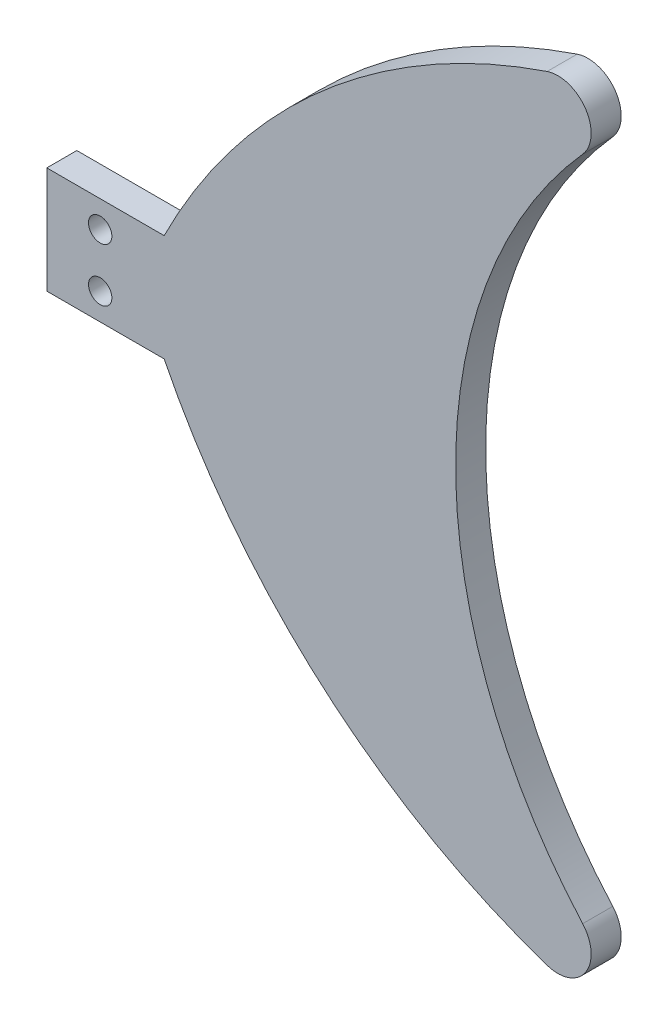
SolidWorks part; units mm, degrees
ref_plane "前视基准面" through (0, 0, 0) normal (0, 0, 1) x (1, 0, 0)
ref_plane "上视基准面" through (0, 0, 0) normal (0, 1, 0) x (1, 0, 0)
ref_plane "右视基准面" through (0, 0, 0) normal (1, 0, 0) x (0, 0, -1)
sketch "草图1" plane through (0, 0, 0) normal (0, 0, 1) x (1, 0, 0)
  line L0 (-43.1897, 0) -> (51.145, 0) construction
  line L1 (0, 42.1426) -> (0, -43.1152) construction
  line L2 (6, 12) -> (37.7485, 60)
  line L3 (-6, -12) -> (6, -12)
  line L4 (-6, -12) -> (-6, 12)
  line L5 (-6, 12) -> (6, 12)
  line L7 (-6, -12) -> (6, 12) construction
  line L8 (-6, 12) -> (6, -12) construction
  line L9 (6, -12) -> (37.7485, -60)
  arc A0 (37.7485, -60) -> (37.7485, 60) centre (-1.9371, 0) ccw
  point P5 (0, 0)
  dimension "D4" = 70
  dimension "D1" = 24
  dimension "D2" = 12
  dimension "D3" = 120
extrude "凸台-拉伸1" add sketch "草图1" along normal blind 4.5
sketch "草图2" plane through (0, 0, 4.5) normal (0, 0, 1) x (1, 0, 0)
  line L0 (-6, 0) -> (7.5637, 0) construction
  line L1 (-6, 12) -> (-6, -12) construction
  circle A0 centre (0, 5) radius 1.25
  circle A1 centre (0, -5) radius 1.25
  dimension "D1" = 10
  dimension "D2" = 2.5
  dimension "D3" = 6
extrude "切除-拉伸1" cut sketch "草图2" against normal blind 10
sketch "草图3" plane through (0, 0, 4.5) normal (0, 0, 1) x (1, 0, 0)
  line L0 (37.7485, 60) -> (6, 12) construction
  line L1 (-6, 12) -> (6, 12)
  line L2 (-6, 12) -> (-6, 10)
  line L3 (-6, 10) -> (6, 10)
  line L4 (6, 12) -> (6, 10)
  line L6 (-6, -12) -> (6, -12)
  line L7 (-6, -12) -> (-6, -10)
  line L8 (-6, -10) -> (6, -10)
  line L9 (6, -12) -> (6, -10)
  dimension "D1" = 2
  dimension "D2" = 2
extrude "切除-拉伸2" cut sketch "草图3" against normal blind 10
sketch "草图4" plane through (0, 0, 4.5) normal (0, 0, 1) x (1, 0, 0)
  line L1 (9, -15) -> (-4, -15)
  line L2 (9, -15) -> (9, 15)
  line L3 (9, 15) -> (-4, 15)
  line L4 (-4, -15) -> (-4, 15)
  line L6 (-6, 0) -> (9, 0) construction
  line L7 (-6, 10) -> (-6, -10) construction
  line L8 (6, 10) -> (6, 12) construction
  dimension "D1" = 10
  dimension "D2" = 30
  dimension "D3" = 13
extrude "凸台-拉伸2" add sketch "草图4" along normal blind 4
sketch "草图5" plane through (0, 0, 0) normal (0, 0, -1) x (-1, 0, 0)
  line L0 (-7.9843, 15) -> (4, 15) construction
  line L1 (4, -15) -> (-9, -15)
  line L2 (4, -15) -> (4, 15)
  line L3 (4, 15) -> (-9, 15)
  line L4 (-9, -15) -> (-9, 15)
  dimension "D1" = 13
extrude "凸台-拉伸3" add sketch "草图5" along normal blind 4
sketch "草图6" plane through (0, 15, 0) normal (0, 1, 0) x (1, 0, 0)
  line L1 (9, 4) -> (-4, 4)
  line L2 (9, 4) -> (9, -8.5)
  line L3 (9, -8.5) -> (-4, -8.5)
  line L4 (-4, 4) -> (-4, -8.5)
extrude "凸台-拉伸4" add sketch "草图6" against normal blind 3
mirror "镜向1" about plane through (0, 0, 0) normal (0, 1, 0) of "凸台-拉伸4"
ref_plane "基准面1" through (0, 0, 2.25) normal (0, 0, 1) x (1, 0, 0)
sketch "草图8" plane through (0, 0, 2.25) normal (0, 0, 1) x (1, 0, 0)
  line L0 (-4, 15) -> (37.7485, 60)
  line L2 (-4, 15) -> (7.9843, 15)
  line L3 (7.9843, 15) -> (37.7485, 60)
extrude "凸台-拉伸5" add sketch "草图8" along normal up to surface and the other way up to surface up to face at (23.6195, 0, 4.5) other way up to face at (23.6195, 0, 0)
mirror "镜向2" about plane through (0, 0, 0) normal (0, 1, 0) of "凸台-拉伸5"
sketch "草图9" plane through (-4, 0, 0) normal (-1, 0, 0) x (0, 0, 1)
  line L0 (0, 10) -> (0, 12)
  line L1 (0, 12) -> (4.5, 12)
  line L2 (4.5, 12) -> (4.5, 10)
  line L3 (4.5, -10) -> (4.5, -12)
  line L4 (0, 10) -> (0, -10)
  line L5 (0, -10) -> (4.5, -10)
  line L6 (4.5, -10) -> (4.5, 10)
  line L7 (4.5, 10) -> (0, 10)
  line L8 (0, 10) -> (0, -10)
  line L9 (4.5, -12) -> (0, -12)
  line L10 (4.5, -10) -> (4.5, 10)
  line L11 (0, -12) -> (0, -10)
  dimension "D1" = 0
extrude "切除-拉伸3" cut sketch "草图9" against normal blind 10.5 and the other way blind 3
sketch "草图14" plane through (0, 0, 8.5) normal (0, 0, 1) x (1, 0, 0)
  line L4 (-4, 15) -> (-4, -15)
  line L5 (-4, -15) -> (9, -15)
  line L6 (9, -15) -> (9, 15)
  line L7 (9, 15) -> (-4, 15)
  line L8 (-4, 15) -> (-4, -15)
  line L9 (-4, -15) -> (9, -15)
  line L10 (9, -15) -> (9, 15)
  line L11 (9, 15) -> (-4, 15)
  dimension "D1" = 0
extrude "切除-拉伸6" cut sketch "草图14" against normal blind 30
sketch "草图16" plane through (0, 0, 4.5) normal (0, 0, 1) x (1, 0, 0)
  line L0 (9, -15) -> (9, 15) construction
  line L1 (9, 15) -> (-4, 15) construction
  line L2 (-4, -15) -> (9, -15) construction
  line L3 (9, -15) -> (9, 15)
  line L4 (9, 15) -> (-4, 15)
  line L5 (-4, -15) -> (9, -15)
  line L6 (-4, 15) -> (-4, -15)
extrude "凸台-拉伸6" add sketch "草图16" against normal up to surface (4.5 mm away) up to face at (19.6248, 0, 0)
sketch "草图17" plane through (0, 0, 4.5) normal (0, 0, 1) x (1, 0, 0)
  arc A0 (37.7485, -60) -> (37.7485, 60) centre (-1.9371, 0) ccw construction
  point P0 (70, 0)
sketch "草图18" plane through (0, 0, 4.5) normal (0, 0, 1) x (1, 0, 0)
  line L0 (-4, 0) -> (70, 0) construction
  line L1 (-4, 15) -> (-4, -15) construction
  line L2 (-4, 15) -> (65.3824, 15) construction
  line L3 (-4, -15) -> (65.3824, -15) construction
  line L4 (37.7485, 60) -> (6, 15)
  line L5 (6, 15) -> (-4, 15)
  line L6 (-4, 15) -> (37.7485, 60)
  line L7 (-4, -15) -> (37.7485, -60)
  line L8 (6, -15) -> (-4, -15)
  line L9 (37.7485, -60) -> (6, -15)
  dimension "D1" = 10
extrude "切除-拉伸7" cut sketch "草图18" against normal blind 30
sketch "草图19" plane through (-4, 0, 0) normal (-1, 0, 0) x (0, 0, 1)
  line L0 (2.25, -15) -> (2.25, 15) construction
  line L1 (2.25, -39.9189) -> (2.25, 39.9189) construction
  line L2 (4.5, 15) -> (0, 15) construction
  line L3 (4.5, 0) -> (0, 0) construction
  ellipse E0 centre (2.25, 0) end of major axis (2.25, 16) minor radius 9
  dimension "D1" = 32
  dimension "D2" = 18
extrude "凸台-拉伸7" add sketch "草图19" along normal blind 1 and the other way blind 12
sketch "草图20" plane through (-5, 0, 0) normal (-1, 0, 0) x (0, 0, 1)
  line L0 (-6.75, 0) -> (11.25, 0) construction
  line L1 (2.25, 16) -> (2.25, -16) construction
  line L2 (2.25, -39.9189) -> (2.25, 39.9189) construction
  line L4 (0, -8.25) -> (4.5, -8.25)
  line L5 (0, -8.25) -> (0, 8.25)
  line L6 (0, 8.25) -> (4.5, 8.25)
  line L7 (4.5, -8.25) -> (4.5, 8.25)
  ellipse E0 centre (2.25, 0) end of major axis (2.25, 16) minor radius 9 construction
  dimension "D1" = 16.5
  dimension "D2" = 4.5
extrude "切除-拉伸8" cut sketch "草图20" against normal blind 10.5
ref_plane "基准面2" through (5, 0, 0) normal (-1, 0, 0) x (0, 0, 1)
sketch "草图21" plane through (5, 0, 0) normal (-1, 0, 0) x (0, 0, 1)
  ellipse E0 centre (2.25, 0) end of major axis (2.25, 19) minor radius 12
  ellipse E1 centre (2.25, 0) end of major axis (2.25, 16) minor radius 9
  ellipse E2 centre (2.25, 0) end of major axis (2.25, 16) minor radius 9
  dimension "D2" = 38
  dimension "D3" = 24
  dimension "D1" = 0
extrude "凸台-拉伸8" add sketch "草图21" against normal blind 5
sketch "草图23" plane through (0, 0, 4.5) normal (0, 0, 1) x (1, 0, 0)
  line L0 (5, 19) -> (37.7485, 60)
  line L1 (5, 19) -> (5, -19) construction
  line L9 (8.8221, 19) -> (5, 19) construction
  line L16 (5, 19) -> (5, 17.2677)
  line L17 (5, 17.2677) -> (10, 17.2677)
  line L18 (10, -18.663) -> (10, 18.663) construction
  line L19 (10, 17.2677) -> (37.7485, 60)
extrude "凸台-拉伸9" add sketch "草图23" against normal up to surface (4.5 mm away) up to face at (18.0917, 0, 0)
mirror "镜向4" about plane through (0, 0, 0) normal (0, 1, 0) of "凸台-拉伸9"
sketch "草图24" plane through (5, 0, 0) normal (-1, 0, 0) x (0, 0, 1)
  line L0 (2.25, -39.9189) -> (2.25, 39.9189) construction
  ellipse E0 centre (2.25, 0) end of major axis (2.25, 16) minor radius 9 construction
  ellipse E1 centre (2.25, 0) end of major axis (2.25, 16) minor radius 9
  ellipse E2 centre (0, 0) end of major axis (-2.25, 22.2358) minor radius 16.6981
extrude "切除-拉伸9" cut sketch "草图24" against normal blind 1
sketch "草图25" plane through (8, 0, 0) normal (1, 0, 0) x (0, 0, -1)
  line L1 (-4.5, -15.4919) -> (-4.5, 15.4919)
  line L2 (-4.5, -15.4919) -> (-4.5, 15.4919)
  ellipse E1 centre (-2.25, 0) end of major axis (-2.25, 16) minor radius 9 (-4.5, 15.4919) -> (-4.5, -15.4919) ccw
  ellipse E2 centre (-2.25, 0) end of major axis (-2.25, 16) minor radius 9 (-4.5, 15.4919) -> (-4.5, -15.4919) ccw
  dimension "D1" = 0
extrude "凸台-拉伸10" add sketch "草图25" along normal up to surface (2 mm away) up to face at (10, 0, 8.625)
sketch "草图26" plane through (8, 0, 0) normal (1, 0, 0) x (0, 0, -1)
  line L1 (0, 15.4919) -> (0, -15.4919)
  line L2 (0, 15.4919) -> (0, -15.4919)
  ellipse E1 centre (-2.25, 0) end of major axis (-2.25, 16) minor radius 9 (0, -15.4919) -> (0, 15.4919) ccw
  ellipse E2 centre (-2.25, 0) end of major axis (-2.25, 16) minor radius 9 (0, -15.4919) -> (0, 15.4919) ccw
  dimension "D1" = 0
extrude "凸台-拉伸11" add sketch "草图26" along normal up to surface (2 mm away) up to face at (10, 0, -4.125)
sketch "草图27" [suppressed] plane through (0, 0, 4.5) normal (0, 0, 1) x (1, 0, 0)
  line L0 (21.8743, 40.126) -> (121.7706, -39.6657) construction
  line L1 (37.7485, 60) -> (6, 20.252) construction
  line L2 (6, 20.252) -> (37.7485, 60)
  circle A0 centre (77.0023, -3.9073) radius 75
  dimension "D1" = 150
fillet "圆角2" radius 5 2 edges at (37.7485, -60, 2.25) (37.7485, 60, 2.25)
sketch "草图29" plane through (0, 0, 4.5) normal (0, 0, 1) x (1, 0, 0)
  line L0 (-1.9371, 0) -> (96.0443, 0) construction
  line L1 (10, 18.663) -> (10, -18.663) construction
  line L2 (6, 20.252) -> (53.8633, 60)
  line L3 (6, -20.252) -> (53.8633, -60)
  line L4 (6, 20.252) -> (41.159, 69.688)
  line L5 (6, -20.252) -> (41.159, -69.688)
  circle A0 centre (-1.9371, 0) radius 81.9371
  point P3 (80, 0)
  line M1 (6, -20.252) -> (34.7985, -56.3067)
  arc M2 (34.7985, -56.3067) -> (41.7411, -57.1591) centre (38.7053, -53.1862) ccw
  arc M3 (41.7411, -57.1591) -> (41.7411, 57.1591) centre (-1.9371, 0) ccw
  arc M4 (41.7411, 57.1591) -> (34.7985, 56.3067) centre (38.7053, 53.1862) ccw
  line M5 (34.7985, 56.3067) -> (6, 20.252)
  dimension "D1" = 70
  dimension "D2" = 120
extrude "凸台-拉伸12" add sketch "草图29" against normal up to surface (4.5 mm away) contours L0 A0 L2 M3 | L0 L3 A0 M3 region at (66.5477, 30.1694, 4.5) region at (66.5477, -30.1694, 4.5) up to face at (22.499, 0, 0)
extrude "切除-拉伸10" cut sketch "草图29<3>" against normal blind 10 contours L2 A0 L4 M5 M4 M3 | L5 A0 L3 M3 M2 M1 | L3 M1 M2 M3 | L2 M5 M3 M4 region at (29.8636, 44.4089, 4.5) region at (24.1403, 44.5712, 4.5) region at (29.8636, -44.4089, 4.5) region at (49.5406, -57.3046, 4.5)
sketch "草图29<3>" plane through (0, 0, 4.5) normal (0, 0, 1) x (1, 0, 0) same geometry as "草图29"
sketch "草图30" plane through (0, 0, 4.5) normal (0, 0, 1) x (1, 0, 0)
  line L0 (29.9317, 40.126) -> (86.0094, -27.4011) construction
  line L1 (6, 20.252) -> (53.8633, 60) construction
  line L2 (6, 20.252) -> (53.8633, 60)
  arc A0 (53.8633, 60) -> (6, 20.252) centre (78.0417, -17.8066) ccw
  arc A1 (53.8633, -60) -> (53.8633, 60) centre (-1.9371, 0) ccw construction
extrude "凸台-拉伸13" [suppressed] add sketch "草图30" against normal up to surface (4.5 mm away)
mirror "镜向5" [suppressed] about plane through (0, 0, 0) normal (0, 1, 0)
fillet "圆角3" radius 5 2 edges at (53.8633, -60, 2.25) (53.8633, 60, 2.25)
sketch "草图31" plane through (-5, 0, 0) normal (-1, 0, 0) x (0, 0, 1)
  line L0 (0, 8.25) -> (0, -8.25) construction
  circle A0 centre (0, 0) radius 27.6373
extrude "切除-拉伸11" cut sketch "草图31" against normal blind 11
sketch "草图32" plane through (6, 0, 0) normal (-1, 0, 0) x (0, 0, 1)
  line L0 (0, 20.252) -> (0, -20.252)
  line L1 (4.5, 20.252) -> (4.5, -20.252)
  line L2 (0, 20.252) -> (-10.5924, 20.252)
  line L3 (-10.5924, 20.252) -> (-10.5924, -20.252)
  line L4 (-10.5924, -20.252) -> (0, -20.252)
  line L5 (4.5, -20.252) -> (15.9387, -20.252)
  line L6 (15.9387, -20.252) -> (15.9387, 20.252)
  line L7 (15.9387, 20.252) -> (4.5, 20.252)
extrude "切除-拉伸12" cut sketch "草图32" against normal blind 10
sketch "草图33" plane through (0, 0, 0) normal (0, 0, -1) x (-1, 0, 0)
  circle A0 centre (-53.5798, 53.2653) radius 5
  arc A1 (-50.3855, 57.1118) -> (-57.1878, 56.7269) centre (-53.5798, 53.2653) ccw construction
  circle A2 centre (-53.5798, -53.2653) radius 5
  arc A3 (-57.1878, -56.7269) -> (-50.3855, -57.1118) centre (-53.5798, -53.2653) ccw construction
  arc A4 (-57.3104, -49.9362) -> (-57.3104, 49.9362) centre (-113.2692, 0) ccw
  arc A5 (-57.1878, 56.7269) -> (-57.1878, -56.7269) centre (1.9371, 0) ccw construction
  arc A6 (-57.1878, 56.7269) -> (-57.1878, -56.7269) centre (1.9371, 0) ccw
  arc M4 (-57.1878, 56.7269) -> (-57.1878, -56.7269) centre (1.9371, 0) ccw
  dimension "D1" = 150
extrude "切除-拉伸13" cut sketch "草图33" against normal blind 10 contours A2 A4 A0 M4 region at (59.3316, 0, 0)
sketch "草图34" plane through (6, 0, 0) normal (-1, 0, 0) x (0, 0, 1)
  line L4 (0, -20.252) -> (4.5, -20.252)
  line L5 (4.5, -20.252) -> (4.5, 20.252)
  line L6 (4.5, 20.252) -> (0, 20.252)
  line L7 (0, 20.252) -> (0, -20.252)
  line L8 (0, -20.252) -> (4.5, -20.252)
  line L9 (4.5, -20.252) -> (4.5, 20.252)
  line L10 (4.5, 20.252) -> (0, 20.252)
  line L11 (0, 20.252) -> (0, -20.252)
  dimension "D1" = 0
extrude "凸台-拉伸14" add sketch "草图34" along normal blind 20
sketch "草图36" plane through (-14, 0, 0) normal (-1, 0, 0) x (0, 0, 1)
  line L0 (0, 0) -> (4.5, 0) construction
  line L1 (4.5, -20.252) -> (4.5, 20.252) construction
  line L3 (0, -15) -> (4.5, -15)
  line L4 (0, -15) -> (0, 15)
  line L5 (0, 15) -> (4.5, 15)
  line L6 (4.5, -15) -> (4.5, 15)
  line L7 (0, -15) -> (4.5, 15) construction
  line L8 (0, 15) -> (4.5, -15) construction
  point P5 (2.25, 0)
  dimension "D1" = 30
sketch "草图37" plane through (0, 0, 4.5) normal (0, 0, 1) x (1, 0, 0)
  line L0 (-14, 15) -> (-0.3243, 15)
  line L1 (-14, -15) -> (-14, 15) construction
  line L2 (6, 20.252) -> (-0.3243, 15)
  line L3 (6, 20.252) -> (50.3855, 57.1118) construction
  line L5 (-14, 0) -> (9.7588, 0) construction
  line L6 (6, -20.252) -> (-0.3243, -15)
  line L7 (-14, -15) -> (-0.3243, -15)
  line L8 (-14, 15) -> (-14, 20.252)
  line L9 (-14, 20.252) -> (6, 20.252)
  line L10 (-14, -15) -> (-14, -20.252)
  line L11 (-14, -20.252) -> (6, -20.252)
extrude "切除-拉伸14" cut sketch "草图37" against normal blind 15
sketch "草图38" plane through (0, 0, 4.5) normal (0, 0, 1) x (1, 0, 0)
  line L0 (-6, 15) -> (-6, -15) construction
  line L1 (-14, 15) -> (-0.3243, 15) construction
  line L2 (-0.3243, -15) -> (-14, -15) construction
  line L3 (-14, -15) -> (-14, 15) construction
  line L4 (-6.6247, 0) -> (0, 0) construction
  circle A0 centre (-6, 4) radius 1.75
  circle A1 centre (-6, -4) radius 1.75
  dimension "D3" = 3.5
  dimension "D1" = 8
  dimension "D2" = 8
sketch "草图39" plane through (0, 0, 4.5) normal (0, 0, 1) x (1, 0, 0)
  line L0 (-0.3243, 15) -> (-2.7326, 13)
  line L1 (0, 0) -> (-9.5572, 0) construction
  line L2 (-0.3243, 15) -> (50.3855, 57.1118) construction
  line L3 (-2.7326, 13) -> (-15.1218, 13)
  line L4 (-15.1218, 13) -> (-15.1218, 15)
  line L5 (-15.1218, 15) -> (-0.3243, 15)
  line L6 (-15.1218, -15) -> (-0.3243, -15)
  line L7 (-15.1218, -13) -> (-15.1218, -15)
  line L8 (-2.7326, -13) -> (-15.1218, -13)
  line L9 (-0.3243, -15) -> (-2.7326, -13)
  dimension "D1" = 2
extrude "切除-拉伸16" cut sketch "草图39" against normal blind 10
sketch "草图41" plane through (0, 0, 4.5) normal (0, 0, 1) x (1, 0, 0)
  line L0 (-2.7326, 13) -> (50.3855, 57.1118) construction
  line L1 (-2.7326, 13) -> (50.3855, 57.1118)
  circle A0 centre (84.0295, -36.7226) radius 100
  arc A1 (57.3104, 49.9362) -> (50.3855, 57.1118) centre (53.5798, 53.2653) ccw construction
  arc A2 (51.9772, 58.0015) -> (50.3855, 57.1118) centre (53.5798, 53.2653) ccw
  arc M5 (57.3104, 49.9362) -> (50.3855, 57.1118) centre (53.5798, 53.2653) ccw
  line M6 (50.3855, 57.1118) -> (-2.7326, 13)
  dimension "D1" = 200
extrude "凸台-拉伸15" add sketch "草图41" against normal up to surface (4.5 mm away) contours A0 M5 M6 region at (22.5643, 37.3012, 4.5) up to face at (21.1931, 0, 0)
mirror "镜向6" about plane through (0, 0, 0) normal (0, 1, 0) of "凸台-拉伸15"
sketch "草图42" plane through (0, 0, 4.5) normal (0, 0, 1) x (1, 0, 0)
  line L0 (-14, 8) -> (-5.4126, 8)
  line L1 (-14, -13) -> (-14, 13) construction
  line L2 (0, 0) -> (-11.7926, 0) construction
  line L3 (-14, 8) -> (-14, 13)
  line L4 (-14, 13) -> (-2.7326, 13)
  circle A0 centre (84.0295, -36.7226) radius 100
  arc A1 (51.9772, 58.0015) -> (-2.7326, 13) centre (84.0295, -36.7226) ccw construction
  line M7 (-2.7326, 13) -> (-14, 13)
  line M8 (-14, 13) -> (-14, -13)
  dimension "D1" = 16
extrude "切除-拉伸17" cut sketch "草图42" against normal blind 10 contours A0 L0 M7 M8 region at (-9.0213, 10.6128, 4.5)
mirror "镜向7" about plane through (0, 0, 0) normal (0, 1, 0) of "切除-拉伸17"
sketch "草图45" plane through (-14, 0, 0) normal (-1, 0, 0) x (0, 0, 1)
  line L4 (0, 8) -> (0, -8)
  line L5 (0, -8) -> (4.5, -8)
  line L6 (4.5, -8) -> (4.5, 8)
  line L7 (4.5, 8) -> (0, 8)
  line L8 (0, 8) -> (0, -8)
  line L9 (0, -8) -> (4.5, -8)
  line L10 (4.5, -8) -> (4.5, 8)
  line L11 (4.5, 8) -> (0, 8)
  dimension "D1" = 0
extrude "凸台-拉伸17" add sketch "草图45" along normal blind 9
sketch "草图46" plane through (0, 0, 4.5) normal (0, 0, 1) x (1, 0, 0)
  line L0 (-23, -8) -> (-23, 8) construction
  line L1 (-23.6177, 0) -> (30.8492, 0) construction
  circle A0 centre (-15, 4) radius 1.75
  circle A1 centre (-15, -4) radius 1.75
  dimension "D1" = 3.5
  dimension "D2" = 8
  dimension "D3" = 4
extrude "切除-拉伸18" cut sketch "草图46" against normal through all
